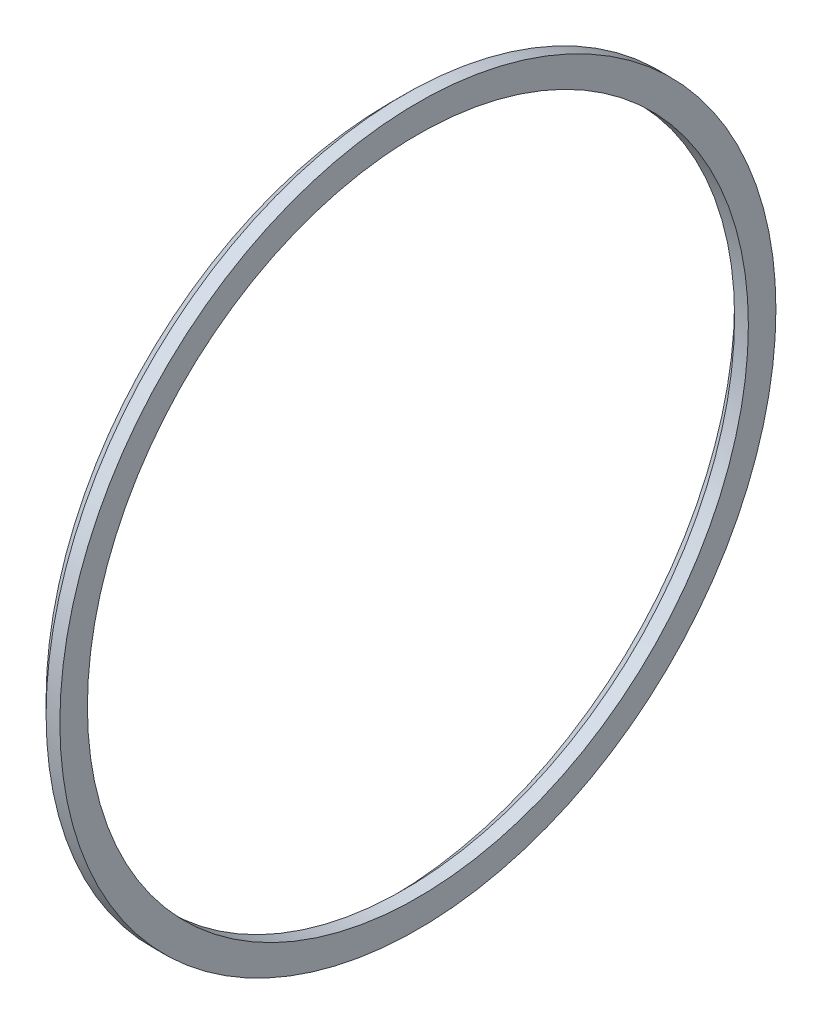
SolidWorks part; units mm, degrees
ref_plane "Front Plane" through (0, 0, 0) normal (1, 0, 0) x (0, 1, 0)
ref_plane "Top Plane" through (0, 0, 0) normal (0, 0, 1) x (0, 1, 0)
ref_plane "Right Plane" through (0, 0, 0) normal (0, 1, 0) x (-1, 0, 0)
sketch "Sketch1" plane through (0, 0, 0) normal (1, 0, 0) x (0, 1, 0)
  circle A0 centre (0, 0) radius 12
  circle A1 centre (0, 0) radius 13
  dimension "D1" = 24
  dimension "D2" = 26
extrude "Boss-Extrude1" add sketch "Sketch1" along normal blind 1
chamfer "Chamfer1" distance 0.5 angle 45 2 edges at (0, 0, -13) (0, 0, -12)
